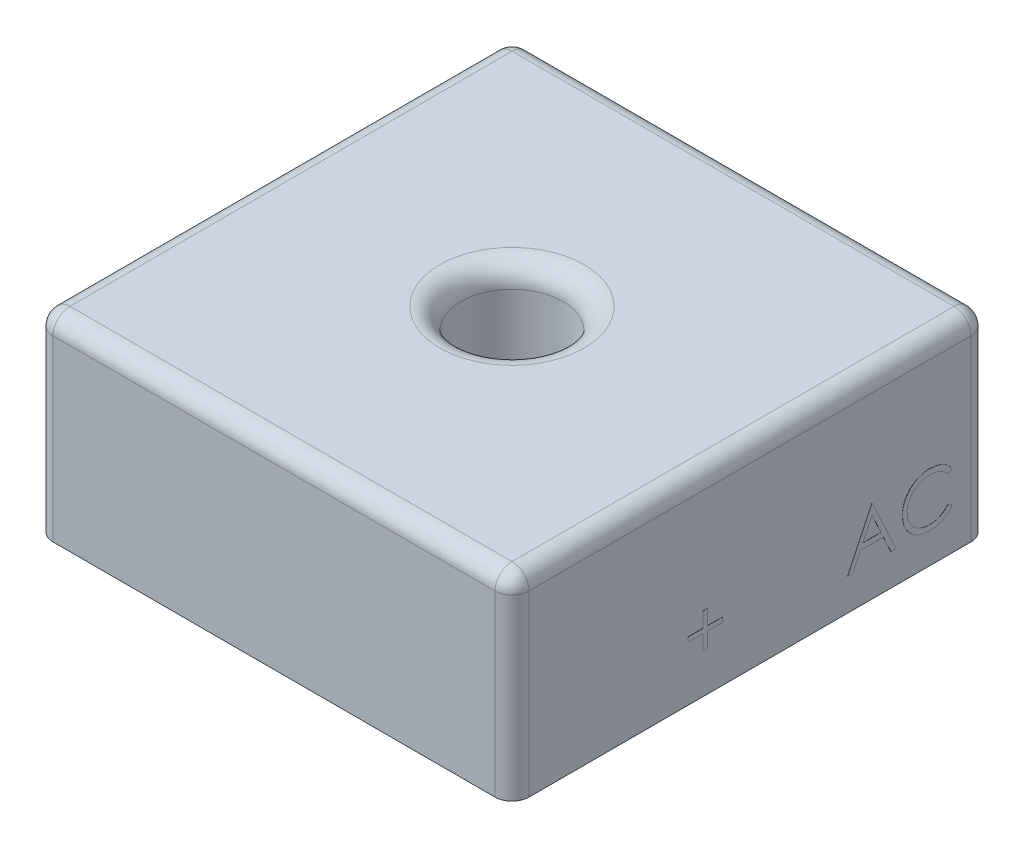
SolidWorks part; units mm, degrees
ref_plane "Front Plane" through (0, 0, 0) normal (0, 0, 1) x (1, 0, 0)
ref_plane "Top Plane" through (0, 0, 0) normal (0, 1, 0) x (1, 0, 0)
ref_plane "Right Plane" through (0, 0, 0) normal (1, 0, 0) x (0, 0, -1)
sketch "Sketch1" plane through (0, 0, 0) normal (0, 1, 0) x (1, 0, 0)
  line L1 (14, 14) -> (-14, 14)
  line L2 (14, 14) -> (14, -14)
  line L3 (14, -14) -> (-14, -14)
  line L4 (-14, 14) -> (-14, -14)
  line L5 (14, 14) -> (-14, -14) construction
  line L6 (14, -14) -> (-14, 14) construction
  circle A0 centre (0, 0) radius 3
  point P0 (0, 0)
  dimension "D3" = 6
  dimension "D1" = 28
  dimension "D2" = 28
extrude "Boss-Extrude1" add sketch "Sketch1" along normal blind 11.5
fillet "Fillet1" radius 1.25 1 edges at (0, 11.5, 3)
sketch "Sketch2" plane through (0, 0, 0) normal (0, -1, 0) x (1, 0, 0)
  line L8 (-12.9, 12.9) -> (-12.9, -12.9)
  line L9 (-12.9, -12.9) -> (12.9, -12.9)
  line L10 (12.9, -12.9) -> (12.9, 12.9)
  line L11 (12.9, 12.9) -> (-12.9, 12.9)
  line L12 (-12.9, 12.9) -> (-12.9, -12.9)
  line L13 (-12.9, -12.9) -> (12.9, -12.9)
  line L14 (12.9, -12.9) -> (12.9, 12.9)
  line L15 (12.9, 12.9) -> (-12.9, 12.9)
  circle A0 centre (0, 0) radius 4
  dimension "D1" = 1.1
extrude "Cut-Extrude1" cut sketch "Sketch2" against normal blind 2.5
sketch "Sketch3" plane through (0, 2.5, 0) normal (0, -1, 0) x (-1, 0, 0)
  line L0 (8.9, -8.9) -> (-19.2445, -8.9) construction
  line L1 (18.8828, 8.9) -> (-8.9, 8.9) construction
  line L2 (8.9, -18.3055) -> (8.9, 8.9) construction
  line L3 (-8.9, -8.9) -> (-8.9, 17.6172) construction
  line L4 (14, 14) -> (14, -14) construction
  line L5 (-14, -14) -> (-14, 14) construction
  line L6 (14, -14) -> (-14, -14) construction
  line L7 (-14, 14) -> (14, 14) construction
  line L8 (-17.082, -2.1) -> (-8.9, -2.1) construction
  circle A0 centre (-8.9, -2.1) radius 0.7
  circle A1 centre (-8.9, 8.9) radius 0.7
  circle A2 centre (8.9, 8.9) radius 0.7
  circle A3 centre (8.9, -8.9) radius 0.7
  dimension "D1" = 5.1
  dimension "D2" = 5.1
  dimension "D3" = 5.1
  dimension "D4" = 5.1
  dimension "D5" = 11
extrude "Boss-Extrude2" add sketch "Sketch3" along normal blind 6.5
sketch "Sketch4" plane through (0, -4, 0) normal (0, -1, 0) x (-1, 0, 0)
  circle A0 centre (8.9, -8.9) radius 0.7
  circle A1 centre (-8.9, -2.1) radius 0.7
  circle A2 centre (-8.9, 8.9) radius 0.7
  circle A3 centre (8.9, 8.9) radius 0.7
extrude "Boss-Extrude3" add sketch "Sketch4" along normal blind 0.5 draft 20
fillet "Fillet2" radius 2.2 9 edges at (12.9, 2.5, 0) (0, 2.5, -12.9) (-12.9, 2.5, 0) (0, 2.5, 12.9) (0, 2.5, -4) (8.9, 2.5, 1.4) (8.9, 2.5, -9.6) (-8.9, 2.5, -9.6) (-8.9, 2.5, 8.2)
fillet "Fillet3" radius 1 8 edges at (-14, 5.75, -14) (-14, 5.75, 14) (0, 11.5, 14) (14, 5.75, 14) (14, 11.5, 0) (14, 5.75, -14) (0, 11.5, -14) (-14, 11.5, 0)
sketch "Sketch5" plane through (14, 0, 0) normal (1, 0, 0) x (0, 0, -1)
  text T0 "+      AC" font "Century Gothic" height 3
extrude "Boss-Extrude4" add sketch "Sketch5" along normal blind 0.01
